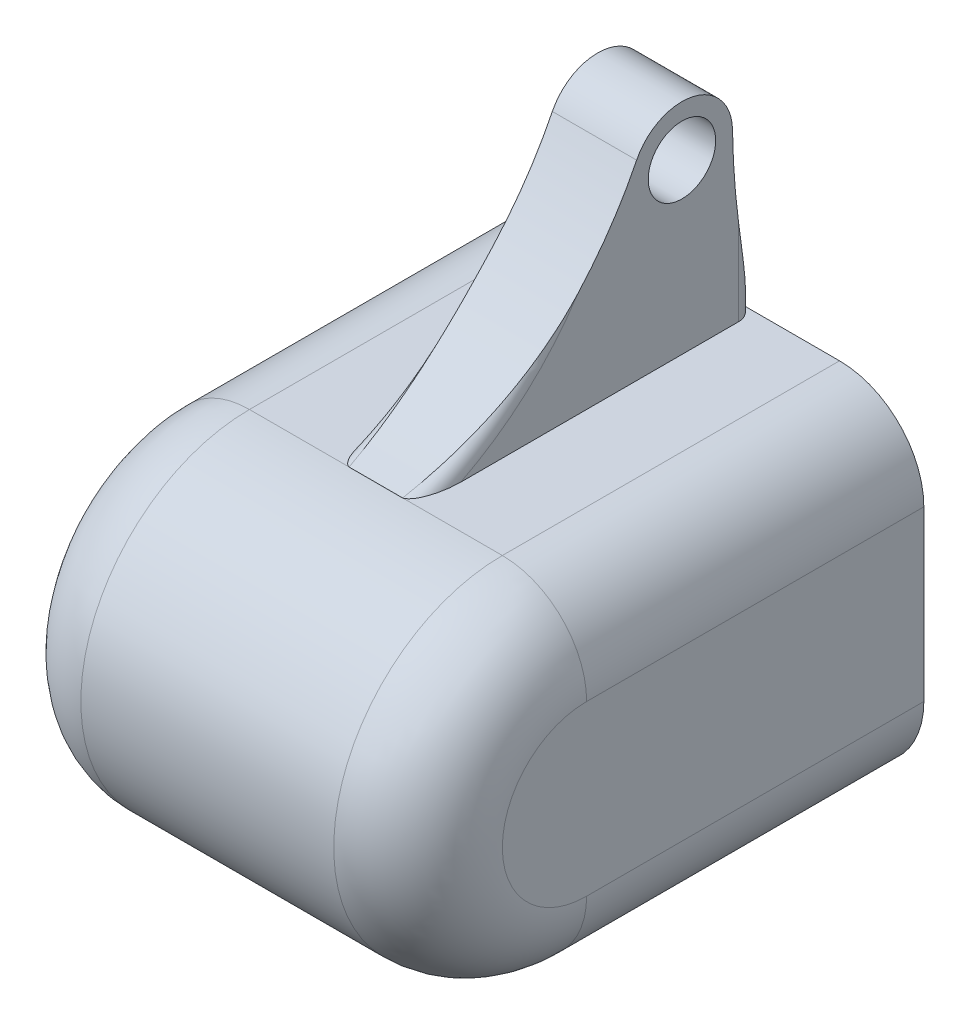
SolidWorks part; units mm, degrees
material "Nailon 6/10"
ref_plane "Alzado" through (0, 0, 0) normal (0, 0, 1) x (1, 0, 0)
ref_plane "Planta" through (0, 0, 0) normal (0, 1, 0) x (1, 0, 0)
ref_plane "Vista lateral" through (0, 0, 0) normal (1, 0, 0) x (0, 0, -1)
sketch "Croquis1" plane through (0, 0, 0) normal (1, 0, 0) x (0, 0, -1)
  line L0 (0, 0) -> (20, 0)
  line L1 (0, 20) -> (20, 20)
  line L2 (20, 20) -> (20, 0)
  arc A0 (0, 0) -> (0, 20) centre (0, 10) cw
  dimension "D2" = 10
  dimension "D1" = 20
  dimension "D3" = 20
extrude "Saliente-Extruir1" add sketch "Croquis1" along normal blind 25
fillet "Redondeo1" radius 5 6 edges at (0, 0, -10) (0, 10, 10) (25, 0, -10) (25, 10, 10) (0, 20, -10) (25, 20, -10)
shell "Vaciado1" thickness 2 removed face at (12.5, 10, -20)
ref_plane "Plano1" through (12.5, 0, 0) normal (1, 0, 0) x (0, 0, -1)
sketch "Croquis3" plane through (12.5, 0, 0) normal (1, 0, 0) x (0, 0, -1)
  line L0 (0, 20) -> (20, 20) construction
  line L1 (20, 20) -> (20, 33.9901)
  line L2 (20, 33.9901) -> (11.3049, 33.9901)
  line L3 (-0.0121, 20) -> (20, 20)
  arc A0 (-0.0121, 20) -> (11.3049, 33.9901) centre (-5.644, 36.1282) ccw
extrude "Saliente-Extruir2" add sketch "Croquis3" along normal mid plane 5
fillet "Redondeo3" radius 1 6 edges at (15, 33.9901, -15.6525) (15, 26.9951, -20) (15, 25.3842, -7.6378) (10, 26.9951, -20) (10, 25.3842, -7.6378) (10, 33.9901, -15.6525)
sketch "Croquis4" plane through (15, 0, 0) normal (1, 0, 0) x (0, 0, -1)
  line L0 (15.6525, 33.9901) -> (15.6525, 20) construction
  line L1 (11.3049, 33.9901) -> (20, 33.9901) construction
  line L2 (19, 20) -> (2.5343, 20) construction
  circle A0 centre (15.6525, 29.9901) radius 2
  dimension "D1" = 4
  dimension "D2" = 4
extrude "Cortar-Extruir1" cut sketch "Croquis4" against normal through all
sketch "Croquis5" plane through (15, 0, 0) normal (1, 0, 0) x (0, 0, -1)
  line L0 (0, 20) -> (20, 20)
  line L2 (-7.217, 39.7816) -> (25.5715, 39.7816)
  line L3 (-7.217, 39.7816) -> (-7.217, 20)
  line L4 (-7.217, 20) -> (25.5715, 20)
  line L5 (25.5715, 39.7816) -> (25.5715, 20)
  circle A0 centre (15.6525, 29.9901) radius 3
  circle A1 centre (15.6525, 29.9901) radius 2 construction
  arc A2 (0, 20) -> (12.9656, 31.3245) centre (-7.217, 41.3474) ccw
  arc A4 (-0.0121, 20) -> (11.3049, 33.9901) centre (-5.644, 36.1282) ccw construction
  arc A5 (20, 20) -> (18.6522, 30.0334) centre (61.2443, 30.6478) cw
  line M2 (19, 32.9901) -> (12.1649, 32.9901)
  arc M3 (12.1649, 32.9901) -> (2.5343, 20) centre (-5.644, 36.1282) cw
  line M5 (19, 20) -> (19, 32.9901)
  dimension "D1" = 1
extrude "Cortar-Extruir2" cut sketch "Croquis5" against normal blind 10 contours A5 L4 L5 L2 L3 A2 M3 M2 M5 | A2 A0 M3 M2 | A5 A0 M5 M2 region at (15, 31.1423, -8.0495) region at (15, 30.9065, -12.2445) region at (15, 27.6083, -18.8415)
ref_plane "Plane1" through (12.5, 0, 0) normal (-1, 0, 0) x (0, 0, 1)
